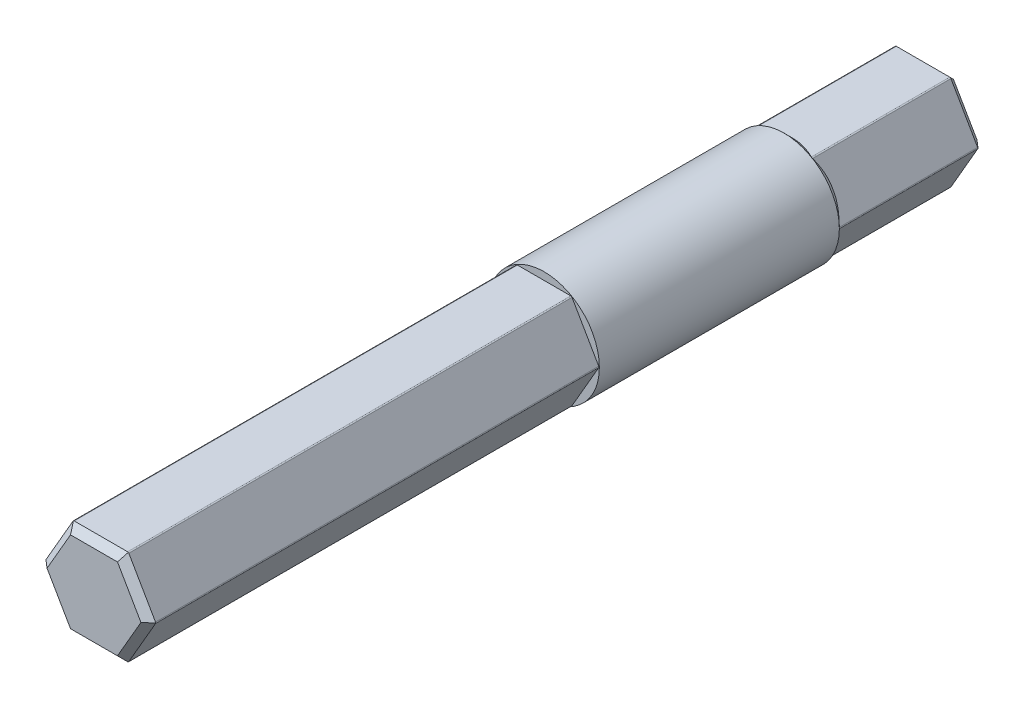
SolidWorks part; units mm, degrees
material "PETG"
ref_plane "Front Plane" through (0, 0, 0) normal (0, 0, 1) x (1, 0, 0)
ref_plane "Top Plane" through (0, 0, 0) normal (0, 1, 0) x (1, 0, 0)
ref_plane "Right Plane" through (0, 0, 0) normal (1, 0, 0) x (0, 0, -1)
sketch "Sketch1" plane through (0, 0, 0) normal (0, 0, 1) x (1, 0, 0)
  circle A0 centre (0, 0) radius 3.975
  dimension "Shaft Dia" = 7.95
extrude "Boss-Extrude1" add sketch "Sketch1" along normal blind 17.775
sketch "Sketch2" plane through (0, 0, 17.775) normal (0, 0, 1) x (1, 0, 0)
  line L1 (4, 0) -> (2, 3.4641) construction
  line L2 (2, 3.4641) -> (-2, 3.4641) construction
  line L3 (-2, 3.4641) -> (-4, 0) construction
  line L4 (-4, 0) -> (-2, -3.4641) construction
  line L5 (-2, -3.4641) -> (2, -3.4641) construction
  line L6 (2, -3.4641) -> (4, 0) construction
  line L7 (3.9567, 0) -> (1.9783, 3.4266)
  line L8 (1.9783, 3.4266) -> (-1.9783, 3.4266)
  line L9 (-1.9783, 3.4266) -> (-3.9567, 0)
  line L10 (-3.9567, 0) -> (-1.9783, -3.4266)
  line L11 (-1.9783, -3.4266) -> (1.9783, -3.4266)
  line L12 (1.9783, -3.4266) -> (3.9567, 0)
  circle A0 centre (0, 0) radius 3.4641 construction
  circle A1 centre (0, 0) radius 3.4266 construction
  dimension "Hex Circumscribed Nominal Dia" = 8
  dimension "Hex Flat To Flat Offset" = 0.0375
extrude "Boss-Extrude2" add sketch "Sketch2" along normal blind 32.4
sketch "Sketch3" plane through (0, 0, 0) normal (0, 0, -1) x (-1, 0, 0)
  line L0 (-1.9783, 3.4266) -> (1.9783, 3.4266) construction
  line L13 (3.9567, 0) -> (1.9783, 3.4266)
  line L14 (1.9783, 3.4266) -> (-1.9783, 3.4266)
  line L15 (-1.9783, 3.4266) -> (-3.9567, 0)
  line L16 (-3.9567, 0) -> (-1.9783, -3.4266)
  line L17 (-1.9783, -3.4266) -> (1.9783, -3.4266)
  line L18 (1.9783, -3.4266) -> (3.9567, 0)
  circle A1 centre (0, 0) radius 3.4266 construction
extrude "Boss-Extrude3" add sketch "Sketch3" along normal blind 10
chamfer "Chamfer1" distance 0.5 angle 45 12 edges at (0, -3.4266, 50.175) (-2.9675, -1.7133, 50.175) (-2.9675, 1.7133, 50.175) (0, 3.4266, 50.175) (2.9675, 1.7133, 50.175) (2.9675, -1.7133, 50.175) (0, -3.4266, -10) (2.9675, -1.7133, -10) (2.9675, 1.7133, -10) (0, 3.4266, -10) (-2.9675, 1.7133, -10) (-2.9675, -1.7133, -10)
fillet "Fillet1" radius 0.1 12 edges at (-1.9783, 3.4266, -4.75) (-3.9567, 0, -4.75) (1.9783, 3.4266, -4.75) (3.9567, 0, -4.75) (1.9783, -3.4266, -4.75) (-1.9783, -3.4266, -4.75) (1.9783, -3.4266, 33.725) (-1.9783, -3.4266, 33.725) (-3.9567, 0, 33.725) (-1.9783, 3.4266, 33.725) (3.9567, 0, 33.725) (1.9783, 3.4266, 33.725)
chamfer "Chamfer2" distance 0.5 angle 45 1 edges at (3.975, 0, 0)
equation "\"tol_dia_id_intfc\" = 0.0500mm ' For hole diameters - Interference fit"
equation "\"tol_dia_id_slip\"  = 0.0750mm ' For hole diameters - Slip fit"
equation "\"tol_dia_id_clear\" = 0.1000mm ' For hole diameters - Clearance fit"
equation "\"tol_dia_od_intfc\" = 0.0500mm ' For shaft diameters - Interference fit"
equation "\"tol_dia_od_slip\"  = 0.0750mm ' For shaft diameters - Slip fit"
equation "\"tol_dia_od_clear\" = 0.1000mm ' For shaft diameters - Clearance fit"
equation "\"tol_general_intfc\"= 0.0250mm ' For general parts (Horiz) - Interference fit"
equation "\"tol_general_slip\" = 0.0375mm ' For general parts (Horiz) - Slip fit"
equation "\"tol_general_clear\"= 0.0500mm ' For general parts (Horiz) - Clearance fit"
equation "\"tol_layer_intfc\"  = 0.0250mm ' For all parts (Vert) - Interference fit"
equation "\"tol_layer_slip\"   = 0.0375mm ' For all parts (Vert) - Slip fit"
equation "\"tol_layer_clear\"  = 0.0500mm ' For all parts (Vert) - Clearance fit"
equation "\"tol_corner_rad\"   = 0.100mm ' For corners that fit into other parts"
equation "\"Shaft Dia@Sketch1\" = \"nominal_dia\" - \"tol_dia_od_intfc\""
equation "\"nominal_dia\"= 8.00mm"
equation "\"Hex Circumscribed Nominal Dia@Sketch2\" = \"nominal_dia\""
equation "\"Hex Flat To Flat Offset@Sketch2\"=\"tol_general_slip\""
equation "\"D1@Fillet1\"=\"tol_corner_rad\""
equation "\"D1@Boss-Extrude2\"=32.50mm-\"tol_layer_clear\"*2"
